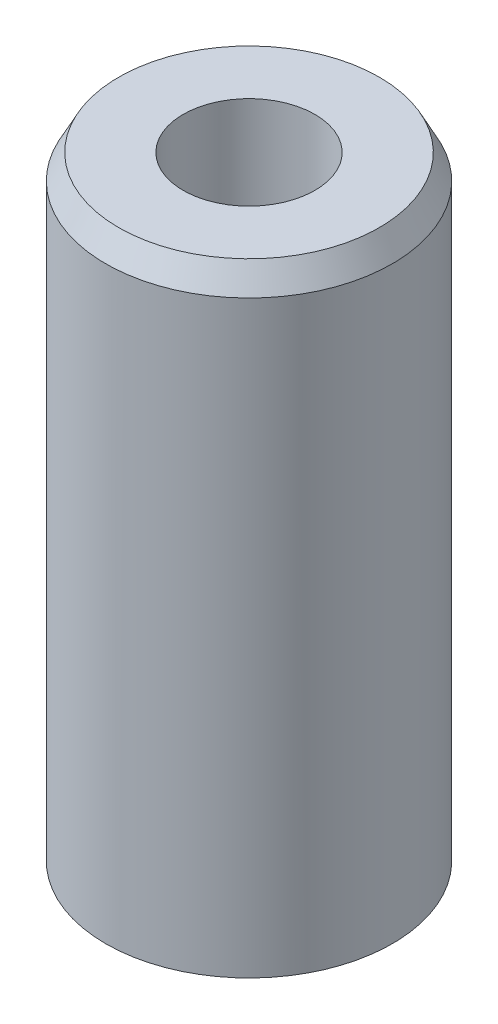
SolidWorks part; units mm, degrees
ref_plane "Front Plane" through (0, 0, 0) normal (0, 0, 1) x (1, 0, 0)
ref_plane "Top Plane" through (0, 0, 0) normal (0, 1, 0) x (1, 0, 0)
ref_plane "Right Plane" through (0, 0, 0) normal (1, 0, 0) x (0, 0, -1)
sketch "Sketch1" plane through (0, 0, 0) normal (0, 1, 0) x (1, 0, 0)
  circle A0 centre (0, 0) radius 27.5
  dimension "SHAFT_OD" = 55
extrude "Boss-Extrude1" add sketch "Sketch1" along normal blind 120.2255
sketch "Sketch2" plane through (0, 0, 0) normal (0, 1, 0) x (1, 0, 0)
  circle A0 centre (0, 0) radius 12.639
  dimension "BORE_D" = 25.278
extrude "Cut-Extrude1" cut sketch "Sketch2" along normal through all
chamfer "Chamfer1" distance 4.7551 angle 27.685 2 edges at (0, 120.2255, 27.5) (0, 0, 27.5) first distance on face at (0, 120.2255, 27.5) first distance on face at (0, 0, 12.639)
